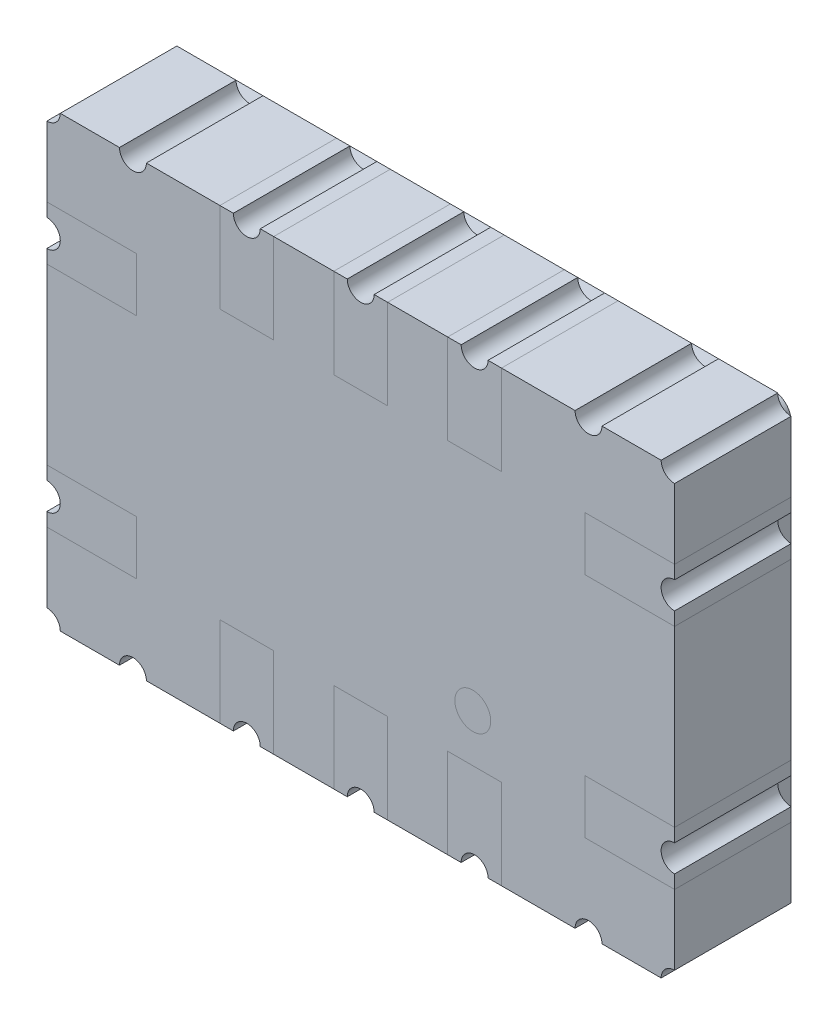
SolidWorks part; units mm, degrees
ref_plane "Front Plane" through (0, 0, 0) normal (0, 0, 1) x (1, 0, 0)
ref_plane "Top Plane" through (0, 0, 0) normal (0, 1, 0) x (1, 0, 0)
ref_plane "Right Plane" through (0, 0, 0) normal (1, 0, 0) x (0, 0, -1)
sketch "Sketch1" plane through (0, 0, 0) normal (0, 0, 1) x (1, 0, 0)
  line L1 (-3.5, 2.5) -> (3.5, 2.5)
  line L2 (-3.5, 2.5) -> (-3.5, -2.5)
  line L3 (-3.5, -2.5) -> (3.5, -2.5)
  line L4 (3.5, 2.5) -> (3.5, -2.5)
  line L5 (-3.5, 2.5) -> (3.5, -2.5) construction
  line L6 (-3.5, -2.5) -> (3.5, 2.5) construction
  point P0 (0, 0)
  dimension "D1" = 7
  dimension "D2" = 5
extrude "Boss-Extrude1" add sketch "Sketch1" along normal blind 1.5
sketch "Sketch2" plane through (0, 0, 1.5) normal (0, 0, 1) x (1, 0, 0)
  line L0 (-3.5, 2.5) -> (-3.5, -2.5) construction
  line L1 (-3.5, -2.5) -> (3.5, -2.5) construction
  line L2 (-3.5, -2.35) -> (-3.5, -2.5)
  line L3 (-3.5, -2.5) -> (-3.35, -2.5)
  arc A0 (-3.5, -2.35) -> (-3.35, -2.5) centre (-3.5, -2.5) cw
  dimension "D1" = 0.15
extrude "Cut-Extrude1" cut sketch "Sketch2" against normal blind 1.5
mirror "Mirror1" about plane through (0, 0, 0) normal (0, 1, 0) of "Cut-Extrude1"
mirror "Mirror2" about plane through (0, 0, 0) normal (1, 0, 0) of "Cut-Extrude1", "Mirror1"
sketch "Sketch3" plane through (0, 0, 1.5) normal (0, 0, 1) x (1, 0, 0)
  line L0 (-3.35, -2.5) -> (3.35, -2.5) construction
  line L1 (-1.57, -2.5) -> (-0.97, -2.5)
  line L2 (-1.57, -2.5) -> (-1.57, -1.5)
  line L3 (-1.57, -1.5) -> (-0.97, -1.5)
  line L4 (-0.97, -2.5) -> (-0.97, -1.5)
  line L5 (0.825, 0) -> (-0.825, 0) construction
  line L6 (-0.3, -2.5) -> (0.3, -2.5)
  line L7 (-0.3, -2.5) -> (-0.3, -1.5)
  line L8 (-0.3, -1.5) -> (0.3, -1.5)
  line L9 (0.3, -2.5) -> (0.3, -1.5)
  line L10 (0.97, -2.5) -> (1.57, -2.5)
  line L11 (0.97, -2.5) -> (0.97, -1.5)
  line L12 (0.97, -1.5) -> (1.57, -1.5)
  line L13 (1.57, -2.5) -> (1.57, -1.5)
  line L14 (1.57, 2.5) -> (1.57, 1.5)
  line L15 (0.97, 1.5) -> (1.57, 1.5)
  line L16 (0.97, 2.5) -> (0.97, 1.5)
  line L17 (0.97, 2.5) -> (1.57, 2.5)
  line L18 (0.3, 2.5) -> (0.3, 1.5)
  line L19 (-0.3, 1.5) -> (0.3, 1.5)
  line L20 (-0.3, 2.5) -> (-0.3, 1.5)
  line L21 (-0.3, 2.5) -> (0.3, 2.5)
  line L22 (-0.97, 2.5) -> (-0.97, 1.5)
  line L23 (-1.57, 1.5) -> (-0.97, 1.5)
  line L24 (-1.57, 2.5) -> (-1.57, 1.5)
  line L25 (-1.57, 2.5) -> (-0.97, 2.5)
  line L26 (-3.5, 2.35) -> (-3.5, -2.35) construction
  line L27 (-3.5, 1.57) -> (-2.5, 1.57)
  line L28 (-3.5, 1.57) -> (-3.5, 0.97)
  line L29 (-3.5, 0.97) -> (-2.5, 0.97)
  line L30 (-2.5, 1.57) -> (-2.5, 0.97)
  line L31 (0, -0.825) -> (0, 0.825) construction
  line L32 (2.5, 1.57) -> (2.5, 0.97)
  line L33 (3.5, 0.97) -> (2.5, 0.97)
  line L34 (3.5, 1.57) -> (3.5, 0.97)
  line L35 (3.5, 1.57) -> (2.5, 1.57)
  line L36 (3.5, -1.57) -> (3.5, -0.97)
  line L37 (3.5, -1.57) -> (2.5, -1.57)
  line L38 (2.5, -1.57) -> (2.5, -0.97)
  line L39 (3.5, -0.97) -> (2.5, -0.97)
  line L40 (-3.5, -1.57) -> (-3.5, -0.97)
  line L41 (-3.5, -0.97) -> (-2.5, -0.97)
  line L42 (-2.5, -1.57) -> (-2.5, -0.97)
  line L43 (-3.5, -1.57) -> (-2.5, -1.57)
  line L44 (3.35, 2.5) -> (-3.35, 2.5) construction
  line L45 (2.39, 2.5) -> (2.69, 2.5)
  line L46 (2.39, -2.5) -> (2.69, -2.5)
  line L47 (-2.39, 2.5) -> (-2.69, 2.5)
  line L48 (-2.39, -2.5) -> (-2.69, -2.5)
  arc A0 (-1.42, -2.5) -> (-1.12, -2.5) centre (-1.27, -2.5) cw
  arc A1 (-0.15, -2.5) -> (0.15, -2.5) centre (0, -2.5) cw
  arc A2 (1.42, -2.5) -> (1.12, -2.5) centre (1.27, -2.5) ccw
  arc A3 (1.42, 2.5) -> (1.12, 2.5) centre (1.27, 2.5) cw
  arc A4 (-0.15, 2.5) -> (0.15, 2.5) centre (0, 2.5) ccw
  arc A5 (-1.42, 2.5) -> (-1.12, 2.5) centre (-1.27, 2.5) ccw
  arc A6 (-3.5, 1.42) -> (-3.5, 1.12) centre (-3.5, 1.27) cw
  arc A7 (3.5, 1.42) -> (3.5, 1.12) centre (3.5, 1.27) ccw
  arc A8 (3.5, -1.42) -> (3.5, -1.12) centre (3.5, -1.27) cw
  arc A9 (-3.5, -1.42) -> (-3.5, -1.12) centre (-3.5, -1.27) ccw
  arc A10 (2.39, 2.5) -> (2.69, 2.5) centre (2.54, 2.5) ccw
  arc A11 (2.39, -2.5) -> (2.69, -2.5) centre (2.54, -2.5) cw
  arc A12 (-2.39, 2.5) -> (-2.69, 2.5) centre (-2.54, 2.5) cw
  arc A13 (-2.39, -2.5) -> (-2.69, -2.5) centre (-2.54, -2.5) ccw
  line M14 (3.35, 2.5) -> (-3.35, 2.5)
  line M16 (-3.5, 2.35) -> (-3.5, -2.35)
  line M18 (-3.35, -2.5) -> (3.35, -2.5)
  line M20 (3.5, -2.35) -> (3.5, 2.35)
  dimension "D2" = 0.15
  dimension "D8" = 0.15
  dimension "D10" = 0.15
  dimension "D1" = 0.6
  dimension "D3" = 1.27
  dimension "D4" = 1.27
  dimension "D5" = 1
  dimension "D6" = 1
  dimension "D7" = 0.6
  dimension "D9" = 1.27
  dimension "D11" = 1.27
extrude "Cut-Extrude2" cut sketch "Sketch3" against normal blind 1.3 contours A11 M18 | A10 M14 | A12 M14 | A6 L29 L30 L27 M16 | A9 L43 L42 L41 M16 | A0 L4 L3 L2 M18 | A1 L9 L8 L7 M18 | A2 L13 L12 L11 M18 | A8 L39 L38 L37 M20 | A7 L35 L32 L33 M20 | A3 L16 L15 L14 M14 | A4 L20 L19 L18 M14 | A5 L24 L23 L22 M14 | A0 L1 | A1 L6 | L10 A2 | A8 L36 | L34 A7 | A3 L17 | L25 A5 | L21 A4 | A6 L28 | L40 A9 | A13 L48 | L21 L18 L19 L20 region at (-1.27, -1.9727, 1.5) region at (2.54, -2.4363, 1.5) region at (1.27, -1.9727, 1.5) region at (0, -1.9727, 1.5) region at (-1.27, -2.4363, 1.5) region at (0, -2.4363, 1.5) region at (1.27, -2.4363, 1.5) region at (-2.54, 2.4363, 1.5) region at (-1.27, 1.9727, 1.5) region at (0, 1.9727, 1.5) region at (1.27, 1.9727, 1.5) region at (2.54, 2.4363, 1.5) region at (1.27, 2.4363, 1.5) region at (0, 2.4363, 1.5) region at (-1.27, 2.4363, 1.5) region at (-2.9727, -1.27, 1.5) region at (-2.9727, 1.27, 1.5) region at (-3.4363, 1.27, 1.5) region at (-3.4363, -1.27, 1.5) region at (2.9727, 1.27, 1.5) region at (2.9727, -1.27, 1.5) region at (3.4363, 1.27, 1.5) region at (3.4363, -1.27, 1.5)
extrude "Boss-Extrude2" add sketch "Sketch3<3>" against normal blind 1.3 separate body contours A6 L29 L30 L27 M16 | A9 L43 L42 L41 M16 | A0 L4 L3 L2 M18 | A1 L9 L8 L7 M18 | A2 L13 L12 L11 M18 | A8 L39 L38 L37 M20 | A7 L35 L32 L33 M20 | A3 L16 L15 L14 M14 | A4 L20 L19 L18 M14 | A5 L24 L23 L22 M14 region at (-1.27, -1.9727, 1.5) region at (1.27, -1.9727, 1.5) region at (0, -1.9727, 1.5) region at (-1.27, 1.9727, 1.5) region at (0, 1.9727, 1.5) region at (1.27, 1.9727, 1.5) region at (-2.9727, -1.27, 1.5) region at (-2.9727, 1.27, 1.5) region at (2.9727, 1.27, 1.5) region at (2.9727, -1.27, 1.5)
sketch "Sketch3<3>" plane through (0, 0, 1.5) normal (0, 0, 1) x (1, 0, 0) same geometry as "Sketch3"
sketch "Sketch4" plane through (0, 0, 1.5) normal (0, 0, 1) x (1, 0, 0)
  circle A0 centre (1.25, -0.97) radius 0.2
  dimension "D1" = 0.4
  dimension "D2" = 1.25
  dimension "D3" = 0.97
extrude "Cut-Extrude3" cut sketch "Sketch4" against normal blind 1.3 contours A0
extrude "Boss-Extrude3" add sketch "Sketch4<3>" against normal blind 1.3 separate body
sketch "Sketch4<3>" plane through (0, 0, 1.5) normal (0, 0, 1) x (1, 0, 0) same geometry as "Sketch4"
sketch "Sketch5" plane through (0, 0, 0) normal (0, 0, -1) x (-1, 0, 0)
  circle A0 centre (2.5, 1) radius 0.3
  circle A1 centre (2.5, 0) radius 0.3
  circle A2 centre (2.5, -1) radius 0.3
  point P7 (0, 0)
  dimension "D1" = 0.6
  dimension "D2" = 1
  dimension "D3" = 1
  dimension "D4" = 2.5
extrude "Cut-Extrude4" cut sketch "Sketch5" against normal blind 0.1
pattern_linear "LPattern1" count 6 spacing 1 along (1, 0, 0) of "Cut-Extrude4"
sketch "Sketch6" plane through (0, 0, 0) normal (0, 0, -1) x (-1, 0, 0)
  line L0 (3.5, 2.35) -> (3.5, -2.35) construction
  line L1 (3.3, 2.3) -> (-3.3, 2.3)
  line L2 (3.3, 2.3) -> (3.3, -2.3)
  line L3 (3.3, -2.3) -> (-3.3, -2.3)
  line L4 (-3.3, 2.3) -> (-3.3, -2.3)
  line L5 (3.3, 2.3) -> (-3.3, -2.3) construction
  line L6 (3.3, -2.3) -> (-3.3, 2.3) construction
  line L7 (3.35, -2.5) -> (-3.35, -2.5) construction
  line L8 (-3.5, -2.35) -> (-3.5, 2.35) construction
  line L9 (-3.35, 2.5) -> (3.35, 2.5) construction
  line L10 (3.5, 2.35) -> (3.5, -2.35)
  line L11 (3.35, -2.5) -> (-3.35, -2.5)
  line L12 (-3.5, -2.35) -> (-3.5, 2.35)
  line L13 (-3.35, 2.5) -> (3.35, 2.5)
  arc A0 (3.35, 2.5) -> (3.5, 2.35) centre (3.5, 2.5) ccw construction
  arc A1 (3.5, -2.35) -> (3.35, -2.5) centre (3.5, -2.5) ccw construction
  arc A2 (-3.35, -2.5) -> (-3.5, -2.35) centre (-3.5, -2.5) ccw construction
  arc A3 (-3.5, 2.35) -> (-3.35, 2.5) centre (-3.5, 2.5) ccw construction
  arc A4 (3.35, 2.5) -> (3.5, 2.35) centre (3.5, 2.5) ccw
  arc A5 (3.5, -2.35) -> (3.35, -2.5) centre (3.5, -2.5) ccw
  arc A6 (-3.35, -2.5) -> (-3.5, -2.35) centre (-3.5, -2.5) ccw
  arc A7 (-3.5, 2.35) -> (-3.35, 2.5) centre (-3.5, 2.5) ccw
  point P0 (0, 0)
  dimension "D1" = 4.6
  dimension "D2" = 6.6
extrude "Cut-Extrude5" cut sketch "Sketch6" against normal blind 0.2
fillet "Fillet1" radius 0.2 4 edges at (-3.3, 2.3, 0.1) (-3.3, -2.3, 0.1) (3.3, -2.3, 0.1) (3.3, 2.3, 0.1)
